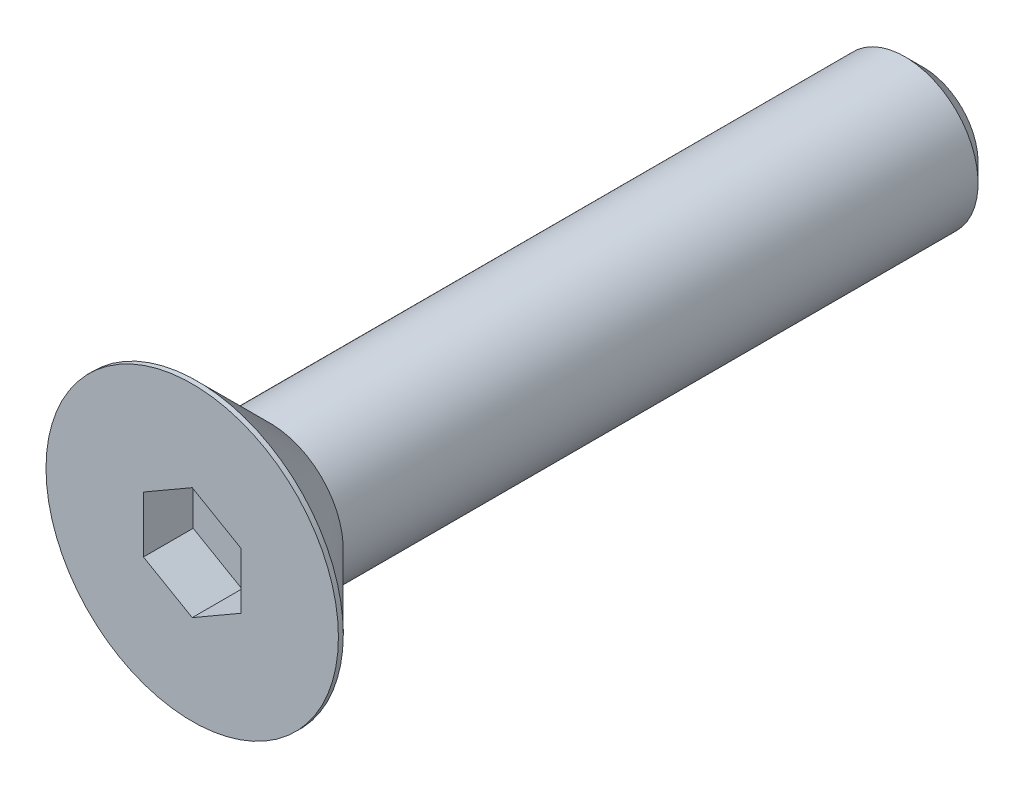
SolidWorks part; units mm, degrees
material "Chrome Stainless Steel"
ref_plane "Front" through (0, 0, 0) normal (0, 0, 1) x (1, 0, 0)
ref_plane "Top" through (0, 0, 0) normal (0, 1, 0) x (1, 0, 0)
ref_plane "Right" through (0, 0, 0) normal (1, 0, 0) x (0, 0, -1)
sketch "Sketch1" plane through (0, 0, 0) normal (0, 0, 1) x (1, 0, 0)
  line L1 (1, 0.5774) -> (0, 1.1547)
  line L8 (0, 1.1547) -> (-1, 0.5774)
  line L9 (-1, 0.5774) -> (-1, -0.5774)
  line L10 (-1, -0.5774) -> (0, -1.1547)
  line L11 (0, -1.1547) -> (1, -0.5774)
  line L12 (1, -0.5774) -> (1, 0.5774)
  circle A0 centre (0, 0) radius 1 construction
  circle A1 centre (0, 0) radius 3
  point P7 (0, 3)
  dimension "Head Diameter" = 6
  dimension "Drive Size" = 2
sketch "Sketch2" plane through (0, 0, 0) normal (1, 0, 0) x (0, 0, -1)
  line L6 (-6.65, 0) -> (6.65, 0) construction
  line L8 (6.65, 0) -> (6.65, 1.5)
  line L9 (6.65, 1.5) -> (-6.65, 1.5)
  line L11 (-6.65, 1.5) -> (-6.65, 0)
  line L13 (-6.65, 1.5) -> (-6.75, 1.5)
  line L14 (-6.75, 1.5) -> (-8.25, 3)
  line L15 (-8.25, 3) -> (-8.35, 3)
  line L16 (-8.35, 3) -> (-8.35, 0)
  line L17 (-8.35, 0) -> (-6.65, 0)
  line L18 (6.65, -1.5) -> (-6.65, -1.5)
  line L19 (-8.25, -3) -> (-8.35, -3)
  line L20 (6.6188, 1.5541) -> (6.8688, 1.1211) construction
  line L21 (6.8688, 1.1211) -> (7.1188, 1.5541) construction
  line L22 (7.1188, 1.5541) -> (6.6188, 1.5541) construction
  line L23 (6.6344, 1.5271) -> (7.1031, 1.5271)
  line L24 (7.1031, 1.5271) -> (6.9, 1.1752)
  line L25 (6.9, 1.1752) -> (6.8375, 1.1752)
  line L26 (6.8375, 1.1752) -> (6.6344, 1.5271)
  line L27 (6.8688, 1.1752) -> (6.8688, 1.1211) construction
  line L28 (6.65, 1.5) -> (7.0875, 1.5) construction
  line L29 (6.8688, 1.5541) -> (6.8688, 1.5) construction
  line L30 (6.275, 1.5) -> (6.65, 1.125)
  point P10 (0, 0)
  point P26 (-7.33, 0)
  point P31 (-1.6, -3)
  point P32 (-0.85, -3)
  point P33 (-0.1, -3)
  point P38 (5.4, -1.5)
  point P51 (6.8688, 1.5271)
  point P53 (-8.35, 3)
  dimension "Thread OD" = 3
  dimension "Head Height" = 1.7
  dimension "D1" = 45
  dimension "Length" = 15
  dimension "Hex Depth" = 1.02
  dimension "D2" = 6.75
  dimension "D3" = 7.5
  dimension "D4" = 6.75
  dimension "Thread Pitch" = 0.5
  dimension "D6" = 0.0625
  dimension "D5" = 45
  dimension "D7" = 0.375
  dimension "D8" = 1.25
ref_plane "Plane1" through (0, 0, 6.65) normal (0, 0, 1) x (1, 0, 0)
sketch "Sketch14" plane through (0, 0, 0) normal (1, 0, 0) x (0, 0, -1)
  line L4 (-8.35, 0) -> (-8.35, 3)
  line L5 (-8.35, 3) -> (-8.25, 3)
  line L6 (-8.25, 3) -> (-6.75, 1.5)
  line L7 (-6.75, 1.5) -> (-6.65, 1.5)
  line L8 (-6.65, 1.5) -> (6.275, 1.5)
  line L9 (6.275, 1.5) -> (6.65, 1.125)
  line L10 (6.65, 1.125) -> (6.65, 0)
  line L11 (6.65, 0) -> (-8.35, 0)
revolve "Revolve1" add sketch "Sketch14" angle 360 about L11
sketch "Sketch3" [suppressed] plane through (0, 0, -6.65) normal (0, 0, -1) x (-1, 0, 0)
  circle A0 centre (0, 0) radius 1.5 construction
  circle A1 centre (0, 0) radius 1.5
sketch "Sketch5" plane through (0, 0, 8.35) normal (0, 0, 1) x (1, 0, 0)
  line L0 (0, -1.1547) -> (1, -0.5774) construction
  line L1 (-1, -0.5774) -> (0, -1.1547) construction
  line L2 (-1, 0.5774) -> (-1, -0.5774) construction
  line L3 (0, 1.1547) -> (-1, 0.5774) construction
  line L4 (1, 0.5774) -> (0, 1.1547) construction
  line L5 (1, -0.5774) -> (1, 0.5774) construction
  line L6 (0, -1.1547) -> (1, -0.5774)
  line L7 (-1, -0.5774) -> (0, -1.1547)
  line L8 (-1, 0.5774) -> (-1, -0.5774)
  line L9 (0, 1.1547) -> (-1, 0.5774)
  line L10 (1, 0.5774) -> (0, 1.1547)
  line L11 (1, -0.5774) -> (1, 0.5774)
extrude "Cut-Extrude2" cut sketch "Sketch5" against normal up to vertex (1.02 mm away) up to point (0, 0, 7.33)
sketch "Sketch6" plane through (0, 0, 8.35) normal (0, 0, 1) x (1, 0, 0)
  circle A0 centre (0, 0) radius 1.1547
extrude "Cut-Extrude3" [suppressed] cut sketch "Sketch6" against normal up to vertex draft 45
split "Split1" [suppressed] bodies to split 134
curve "Helix/Spiral1" [suppressed] pitch 0.5 height 15 turns 30
sketch "Sketch16" [suppressed] plane through (0, 0, 0) normal (1, 0, 0) x (0, 0, -1)
  line L0 (7.1188, 1.5541) -> (6.6187, 1.5541) construction
  line L1 (6.6187, 1.5541) -> (6.8687, 1.1211) construction
  line L2 (6.8687, 1.1211) -> (7.1188, 1.5541) construction
  line L3 (7.0875, 1.5) -> (6.65, 1.5) construction
  line L4 (6.8687, 1.5541) -> (6.8688, 1.5) construction
  line L5 (7.1031, 1.5271) -> (6.6344, 1.5271) construction
  line L6 (6.9, 1.1752) -> (6.8375, 1.1752) construction
  line L7 (6.8688, 1.1752) -> (6.8687, 1.1211) construction
  line L10 (6.9, 1.1752) -> (6.8375, 1.1752)
  line L15 (6.8375, 1.1752) -> (6.6344, 1.5271)
  line L16 (6.6344, 1.5271) -> (7.1031, 1.5271)
  line L17 (7.1031, 1.5271) -> (6.9, 1.1752)
  point P11 (6.8688, 1.5271)
  dimension "D1" = 0.5
  dimension "D2" = 0.0625
sweep "Cut-Sweep1" [suppressed] cut profiles "Sketch16" path "Helix/Spiral1"
sketch "Sketch15" [suppressed] plane through (0, 0, 6.65) normal (0, 0, 1) x (1, 0, 0)
  circle A2 centre (0, 0) radius 1.5
extrude "Boss-Extrude1" [suppressed] add sketch "Sketch15" against normal up to vertex draft 30.9
equation "\"D3@Helix/Spiral1\"=\"Length@Sketch2\""
equation "\"D1\"= \"Head Height@Sketch2\" * .7"
equation "\"D1\"= \"D1\""
equation "\"D4@Helix/Spiral1\" = \"Thread Pitch@Sketch2\""
equation "\"Hex Depth@Sketch2\" = \"Head Height@Sketch2\" * 0.6"
equation "\"D2@Sketch2\" = \"Head Diameter@Sketch1\" * 1.125"
equation "\"D3@Sketch2\" = \"Head Diameter@Sketch1\" * 1.25"
equation "\"D4@Sketch2\" = \"D2@Sketch2\""
equation "\"D6@Sketch2\" = \"Thread Pitch@Sketch2\" / 8"
equation "\"D7@Sketch2\" = \"Thread Pitch@Sketch2\" * 0.75"
equation "\"D8@Sketch2\" = \"Thread Pitch@Sketch2\" * 2.5"
equation "\"D1@Sketch16\"=\"Thread Pitch@Sketch2\""
equation "\"D2@Sketch16\"=\"D1@Sketch16\"/8"
